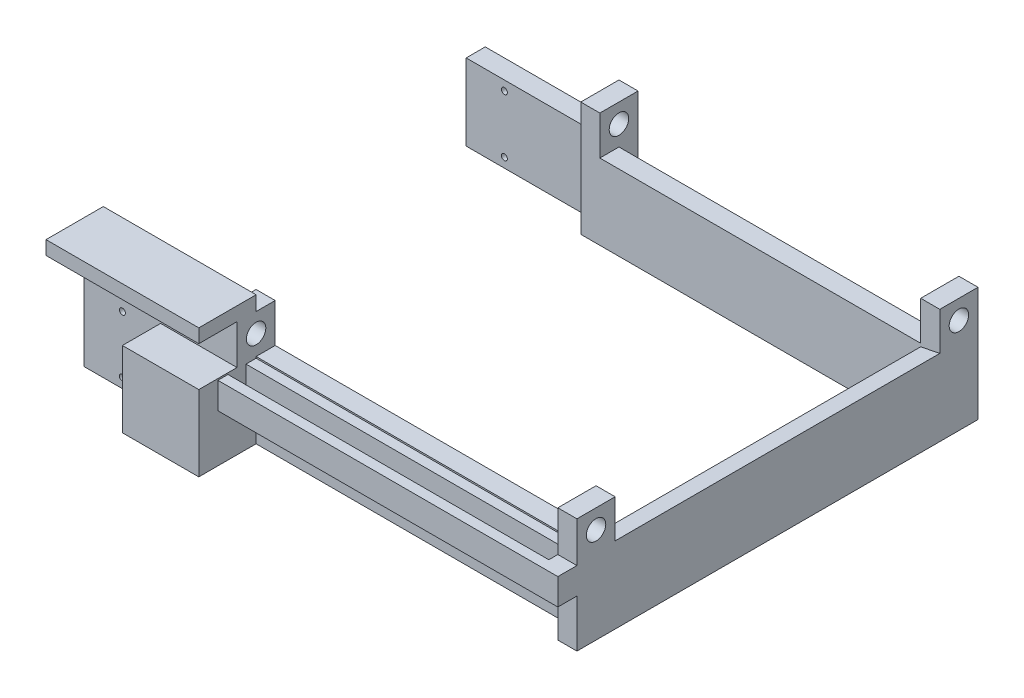
SolidWorks part; units mm, degrees
ref_plane "Front Plane" through (0, 0, 0) normal (0, 0, 1) x (1, 0, 0)
ref_plane "Top Plane" through (0, 0, 0) normal (0, 1, 0) x (1, 0, 0)
ref_plane "Right Plane" through (0, 0, 0) normal (1, 0, 0) x (0, 0, -1)
sketch "Sketch1" plane through (0, 0, 0) normal (0, 1, 0) x (1, 0, 0)
  line L0 (3.175, 114.3) -> (0, 114.3)
  line L1 (0, 0) -> (119.38, 0)
  line L2 (0, 0) -> (0, 6.35)
  line L3 (0, 120.65) -> (119.38, 120.65)
  line L4 (119.38, 0) -> (119.38, 120.65)
  line L5 (3.175, 114.3) -> (113.03, 114.3)
  line L7 (3.175, 6.35) -> (113.03, 6.35)
  line L8 (113.03, 114.3) -> (113.03, 6.35)
  line L9 (3.175, 6.35) -> (0, 6.35)
  line L10 (0, 114.3) -> (0, 120.65)
  dimension "D1" = 120.65
  dimension "D2" = 113.03
  dimension "D3" = 6.35
  dimension "D5" = 6.35
  dimension "D6" = 107.95
extrude "Boss-Extrude1" add sketch "Sketch1" along normal blind 25.4
sketch "Sketch2" plane through (0, 0, 0) normal (0, 0, 1) x (1, 0, 0)
  line L0 (119.38, 25.4) -> (113.03, 24.13)
  line L1 (113.03, 24.13) -> (113.03, 25.4)
  line L2 (0, 25.4) -> (119.38, 25.4) construction
  line L4 (113.03, 25.4) -> (119.38, 25.4)
  dimension "D2" = 1.27
extrude "Cut-Extrude1" cut sketch "Sketch2" against normal up to surface (114.3 mm away) from surface up to face at (56.515, 12.7, -114.3) starting at face at (56.515, 12.7, -6.35)
sketch "Sketch3" plane through (0, 0, 0) normal (0, 0, 1) x (1, 0, 0)
  line L0 (0, 25.4) -> (119.38, 25.4) construction
  line L1 (6.35, 25.4) -> (-44.45, 25.4)
  line L2 (6.35, 25.4) -> (6.35, 0)
  line L3 (6.35, 0) -> (-44.45, 0)
  line L4 (-44.45, 25.4) -> (-44.45, 0)
  line L5 (0, 25.4) -> (0, 0) construction
  dimension "D1" = 6.35
  dimension "D2" = 44.45
extrude "Boss-Extrude2" add sketch "Sketch3" along normal blind 6.35
extrude "Boss-Extrude3" add sketch "Sketch3<2>" against normal blind 6.35 from surface starting at face at (59.69, 12.7, -120.65)
sketch "Sketch3<2>" plane through (0, 0, 0) normal (0, 0, 1) x (1, 0, 0) same geometry as "Sketch3"
sketch "Sketch8" plane through (0, 25.4, 0) normal (0, 1, 0) x (1, 0, 0)
  line L0 (119.38, 60.325) -> (-5.0576, 60.325) construction
  line L1 (119.38, -6.35) -> (113.03, -6.35)
  line L2 (119.38, -6.35) -> (119.38, 6.35)
  line L4 (113.03, -6.35) -> (113.03, 6.35)
  line L5 (113.03, 6.35) -> (119.38, 6.35)
  line L6 (59.69, 114.3) -> (59.69, -20.9935) construction
  line L7 (0, 114.3) -> (119.38, 114.3) construction
  line L8 (119.38, 114.3) -> (119.38, 6.35) construction
  line L9 (6.35, -6.35) -> (6.35, 6.35)
  line L10 (0, 6.35) -> (6.35, 6.35)
  line L11 (0, -6.35) -> (0, 6.35)
  line L12 (0, -6.35) -> (6.35, -6.35)
  line L22 (0, 127) -> (6.35, 127)
  line L23 (0, 127) -> (0, 114.3)
  line L24 (0, 114.3) -> (6.35, 114.3)
  line L25 (6.35, 127) -> (6.35, 114.3)
  line L26 (113.03, 127) -> (113.03, 114.3)
  line L27 (119.38, 114.3) -> (113.03, 114.3)
  line L28 (119.38, 127) -> (119.38, 114.3)
  line L29 (119.38, 127) -> (113.03, 127)
  dimension "D1" = 12.7
extrude "Boss-Extrude4" add sketch "Sketch8" along normal blind 38.1 from surface starting at face at (19.5263, 0, -60.325)
sketch "Sketch9" plane through (119.38, 0, 0) normal (1, 0, 0) x (0, 0, -1)
  line L0 (-6.35, 38.1) -> (6.35, 38.1) construction
  line L3 (60.325, 36.7762) -> (60.325, 19.9574) construction
  line L4 (6.35, 38.1) -> (6.35, 0) construction
  line L5 (-6.35, 38.1) -> (-6.35, 0) construction
  circle A0 centre (0, 31.75) radius 3.2385
  circle A1 centre (120.65, 31.75) radius 3.2385
  dimension "D1" = 6.477
  dimension "D4" = 53.975
  dimension "D2" = 6.35
  dimension "D3" = 6.35
extrude "Cut-Extrude2" cut sketch "Sketch9" against normal through all both and the other way through all
sketch "Sketch10" plane through (0, 0, 6.35) normal (0, 0, 1) x (1, 0, 0)
  line L0 (0, 25.4) -> (-44.45, 25.4) construction
  line L1 (-44.45, 25.4) -> (-44.45, 0) construction
  circle A0 centre (-31.75, 22.225) radius 1
  circle A1 centre (-31.75, 3.175) radius 1
  dimension "D2" = 2
  dimension "D4" = 2
  dimension "D1" = 3.175
  dimension "D3" = 12.7
  dimension "D5" = 19.05
  dimension "D6" = 12.7
extrude "Cut-Extrude3" cut sketch "Sketch10" against normal through all
sketch "Sketch11" plane through (0, 0, 6.35) normal (0, 0, 1) x (1, 0, 0)
  line L0 (-44.45, 0) -> (6.35, 0) construction
  line L1 (6.35, 25.146) -> (-19.05, 25.146)
  line L2 (6.35, 25.146) -> (6.35, 0)
  line L3 (6.35, 0) -> (-19.05, 0)
  line L4 (-19.05, 25.146) -> (-19.05, 0)
  line L5 (0, 25.4) -> (-44.45, 25.4) construction
  dimension "D1" = 25.4
  dimension "D2" = 0.254
extrude "Boss-Extrude5" add sketch "Sketch11" along normal blind 12.7
sketch "Sketch13" plane through (0, 25.4, 0) normal (0, 1, 0) x (1, 0, 0)
  line L1 (-44.45, 0) -> (0, 0)
  line L2 (-44.45, 0) -> (-44.45, -6.35)
  line L3 (-44.45, -6.35) -> (0, -6.35)
  line L4 (0, 0) -> (0, -6.35)
extrude "Boss-Extrude6" add sketch "Sketch13" along normal up to surface (12.7 mm away) up to face at (3.175, 38.1, 0)
sketch "Sketch15" plane through (0, 0, 6.35) normal (0, 0, 1) x (1, 0, 0)
  line L0 (6.35, 25.146) -> (6.35, 38.1) construction
  line L1 (-44.45, 38.1) -> (6.35, 38.1)
  line L2 (-44.45, 38.1) -> (-44.45, 42.926)
  line L3 (-44.45, 42.926) -> (6.35, 42.926)
  line L4 (6.35, 38.1) -> (6.35, 42.926)
  dimension "D1" = 4.826
extrude "Boss-Extrude7" add sketch "Sketch15" along normal up to surface (12.7 mm away) from surface up to face at (-6.35, 12.573, 19.05) starting at face at (-32.75, 22.225, 0)
sketch "Sketch17" plane through (0, 0, 19.05) normal (0, 0, 1) x (1, 0, 0)
  line L0 (-44.45, 42.926) -> (-44.45, 38.1) construction
  line L1 (6.35, 38.1) -> (-44.45, 38.1)
  line L2 (6.35, 38.1) -> (6.35, 38.354)
  line L3 (6.35, 38.354) -> (-44.45, 38.354)
  line L4 (-44.45, 38.1) -> (-44.45, 38.354)
  dimension "D1" = 0.254
extrude "Cut-Extrude4" cut sketch "Sketch17" against normal up to surface (12.7 mm away) up to face at (-19.05, 21.082, 6.35)
sketch "Sketch19" plane through (6.35, 0, 0) normal (1, 0, 0) x (0, 0, -1)
  line L0 (-19.05, 25.146) -> (-6.35, 25.146) construction
  line L1 (-12.7, 24.638) -> (0, 24.638)
  line L2 (-12.7, 24.638) -> (-12.7, 15.875)
  line L3 (-12.7, 15.875) -> (0, 15.875)
  line L4 (0, 24.638) -> (0, 15.875)
  line L5 (-6.35, 38.1) -> (-6.35, 0) construction
  line L6 (-19.05, 0) -> (0, 0) construction
  dimension "D1" = 0.508
  dimension "D2" = 6.35
  dimension "D3" = 15.875
extrude "Boss-Extrude8" add sketch "Sketch19" along normal up to surface (113.03 mm away) up to face at (119.38, 31.75, 3.2385)
sketch "Sketch20" plane through (0, 0, 0) normal (0, 0, 1) x (1, 0, 0)
  line L1 (113.03, 25.4) -> (6.35, 25.4)
  line L2 (113.03, 25.4) -> (113.03, 25.146)
  line L3 (113.03, 25.146) -> (6.35, 25.146)
  line L19 (6.35, 25.4) -> (6.35, 25.146)
extrude "Cut-Extrude5" cut sketch "Sketch20" against normal through all
sketch "Sketch22" plane through (0, 24.638, 0) normal (0, 1, 0) x (1, 0, 0)
  line L2 (6.35, -3.35) -> (113.03, -3.35)
  line L3 (6.35, -3.35) -> (6.35, -9.35)
  line L4 (6.35, -9.35) -> (113.03, -9.35)
  line L5 (113.03, -3.35) -> (113.03, -9.35)
  line L6 (6.35, 0) -> (6.35, -12.7) construction
  line L7 (113.03, -6.35) -> (113.03, 0) construction
  point P6 (6.35, -6.35)
  point P7 (6.35, -6.35)
  dimension "D1" = 6
extrude "Cut-Extrude6" cut sketch "Sketch22" against normal through all
equation "\"tightTol\" = 0.005in"
equation "\"normTol\"= 0.01in"
equation "\"looseTol\"= 0.02in"
equation "\"D1@Sketch9\"=\"tightTol\"+0.250000in"
equation "\"D2@Sketch10\"=2mm"
equation "\"D4@Sketch10\"=2mm"
equation "\"D2@Sketch11\"=\"normTol\""
equation "\"D1@Sketch17\"=\"normTol\""
equation "\"D1@Sketch15\"=0.200000in-\"normTol\""
equation "\"D1@Sketch19\"=\"looseTol\""
equation "\"D1@Sketch22\"=6mm"
